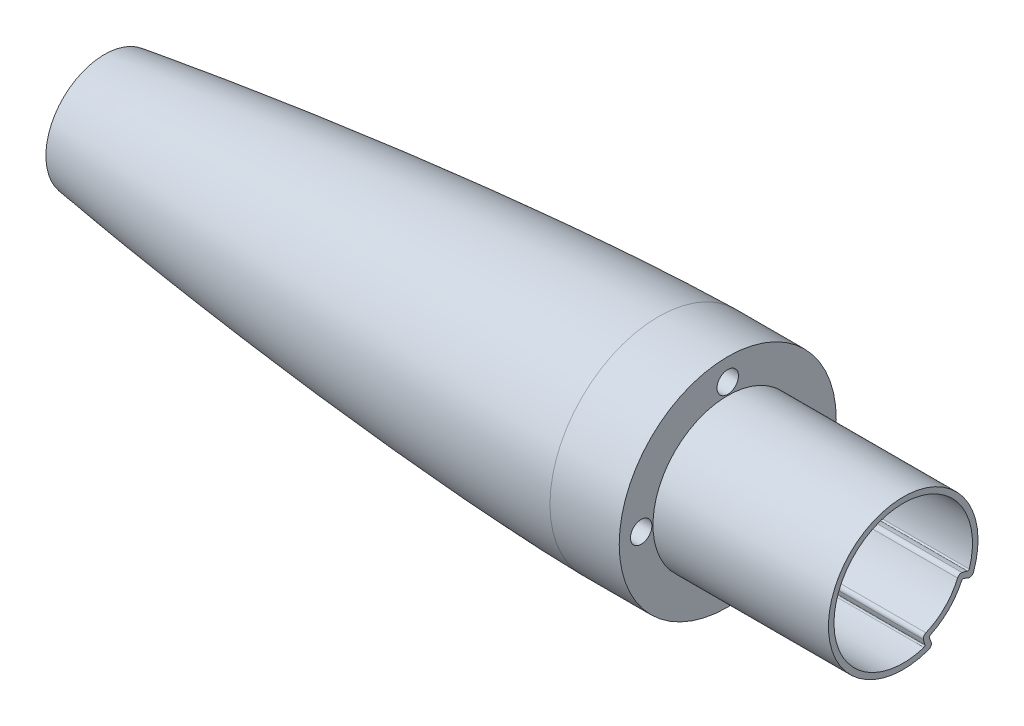
SolidWorks part; units mm, degrees
ref_plane "Front Plane" through (0, 0, 0) normal (0, 0, 1) x (1, 0, 0)
ref_plane "Top Plane" through (0, 0, 0) normal (0, 1, 0) x (1, 0, 0)
ref_plane "Right Plane" through (0, 0, 0) normal (1, 0, 0) x (0, 0, -1)
sketch "Sketch1" plane through (0, 0, 0) normal (0, 0, 1) x (1, 0, 0)
  line L0 (0, 0) -> (600, 0) construction
  line L1 (600, 0) -> (600, 78.36) construction
  line L2 (600, 78.36) -> (650, 78.36)
  line L3 (650, 78.36) -> (650, 54)
  line L4 (650, 54) -> (776.72, 54)
  line L5 (776.72, 54) -> (776.72, 0)
  line L6 (776.72, 0) -> (0, 0)
  line L7 (200, 0) -> (200, 42.3283)
  circle A0 centre (72.0133, 0) radius 20
  spline S0 degree 4 poles (0, 0) (0.0016, 0.0064) (0.0058, 0.0188) (0.0175, 0.0422) (0.0463, 0.0862) (0.0915, 0.1423) (0.1543, 0.2091) (0.2763, 0.3247) (0.4211, 0.4433) (0.5863, 0.5665) (0.8395, 0.741) (1.183, 0.9602) (1.7828, 1.3087) (2.8683, 1.8716) (4.7628, 2.7397) (8.1903, 4.116) (14.423, 6.288) (24.8043, 9.4077) (38.8995, 13.0876) (55.9277, 17.0568) (79.0908, 21.9784) (106.8812, 27.3296) (139.4042, 33.0214) (176.6683, 38.9539) (214.0039, 44.4169) (251.3968, 49.4711) (288.8378, 54.1545) (326.3207, 58.4893) (363.8412, 62.4863) (401.396, 66.1465) (438.983, 69.4606) (476.6007, 72.4071) (509.5423, 74.6287) (537.7965, 76.2335) (560.2923, 77.2755) (575.1954, 77.8326) (587.2142, 78.173) (594.52, 78.3104) (598.1733, 78.3543) (600, 78.36) knots 0 0 0 0 0 0.000043 0.000086 0.000173 0.000345 0.000518 0.00069 0.00128 0.001578 0.001875 0.002717 0.003965 0.006149 0.009932 0.016448 0.028301 0.04964 0.081363 0.112452 0.14354 0.205717 0.267893 0.33007 0.392247 0.454423 0.5166 0.578777 0.640954 0.70313 0.765307 0.827484 0.88966 0.920749 0.951837 0.975919 0.987959 1 1 1 1 1 construction
  spline S1 degree 4 poles (0, 0) (0.0016, 0.0064) (0.0058, 0.0188) (0.0175, 0.0422) (0.0463, 0.0862) (0.0915, 0.1423) (0.1543, 0.2091) (0.2763, 0.3247) (0.4211, 0.4433) (0.5863, 0.5665) (0.8395, 0.741) (1.183, 0.9602) (1.7828, 1.3087) (2.8683, 1.8716) (4.7628, 2.7397) (8.1903, 4.116) (14.423, 6.288) (24.8043, 9.4077) (38.8995, 13.0876) (55.9277, 17.0568) (79.0908, 21.9784) (106.8812, 27.3296) (139.4042, 33.0214) (176.6683, 38.9539) (214.0039, 44.4169) (251.3968, 49.4711) (288.8378, 54.1545) (326.3207, 58.4893) (363.8412, 62.4863) (401.396, 66.1465) (438.983, 69.4606) (476.6007, 72.4071) (509.5423, 74.6287) (537.7965, 76.2335) (560.2923, 77.2755) (575.1954, 77.8326) (587.2142, 78.173) (594.52, 78.3104) (598.1733, 78.3543) (600, 78.36) knots 0 0 0 0 0 0.000043 0.000086 0.000173 0.000345 0.000518 0.00069 0.00128 0.001578 0.001875 0.002717 0.003965 0.006149 0.009932 0.016448 0.028301 0.04964 0.081363 0.112452 0.14354 0.205717 0.267893 0.33007 0.392247 0.454423 0.5166 0.578777 0.640954 0.70313 0.765307 0.827484 0.88966 0.920749 0.951837 0.975919 0.987959 1 1 1 1 1
  dimension "D6" = 40
  dimension "D1" = 78.36
  dimension "D2" = 54
  dimension "D3" = 126.72
  dimension "D4" = 50
  dimension "D5" = 200
revolve "Revolve1" add sketch "Sketch1" angle 360 about L6 region at (496.4687, 32.5271, 0)
sketch "Sketch2" plane through (776.72, 0, 0) normal (1, 0, 0) x (0, 0, -1)
  line L0 (38.1838, -38.1838) -> (0, 0) construction
  line L1 (0, 0) -> (54, 0) construction
  circle A0 centre (0, 0) radius 50
  circle A1 centre (0, 0) radius 54 construction
  circle A2 centre (38.1838, -38.1838) radius 20
  circle A3 centre (0, 0) radius 54 construction
  circle A4 centre (0, 0) radius 42.5
  circle A5 centre (38.1838, -38.1838) radius 24
  circle A6 centre (0, 0) radius 46.5
  circle M1 centre (0, 0) radius 54
  dimension "D1" = 4
  dimension "D3" = 40
  dimension "D4" = 85
  dimension "D5" = 4
  dimension "D2" = 45
  dimension "D6" = 4
extrude "Cut-Extrude1" cut sketch "Sketch2" against normal blind 400 contours A5 A4 | A5 A6 A4 | A6 A5 A0 | A2 A4 | A4 A5 A2 region at (776.72, -7.8832, -47.942) region at (776.72, 26.3344, 36.7174) region at (776.72, -21.4717, -21.4717) region at (776.72, 1.5125, 1.5125) region at (776.72, -27.2667, -27.2667)
sketch "Sketch3" plane through (200, 0, 0) normal (-1, 0, 0) x (0, 0, 1)
  circle A0 centre (0, 20) radius 3.1
  circle A1 centre (0, -20) radius 3.1
  circle A2 centre (0, 0) radius 20 construction
  circle A3 centre (0, 0) radius 33
  dimension "D1" = 6.2
  dimension "D2" = 40
  dimension "D3" = 13
extrude "Cut-Extrude2" cut sketch "Sketch3" against normal blind 40
extrude "Cut-Extrude4" cut sketch "Sketch3<2>" against normal through all contours A0 | A1 region at (200, 20, 0) region at (200, -20, 0)
sketch "Sketch3<2>" plane through (200, 0, 0) normal (-1, 0, 0) x (0, 0, 1) same geometry as "Sketch3"
sketch "Sketch4" plane through (650, 0, 0) normal (1, 0, 0) x (0, 0, -1)
  circle A0 centre (0, 0) radius 62.5 construction
  circle A1 centre (0, 62.5) radius 7.75
  circle A2 centre (62.5, 0) radius 7.75
  circle A3 centre (0, -62.5) radius 7.75
  circle A4 centre (-62.5, 0) radius 7.75
  point P14 (0, 0)
  dimension "D1" = 15.5
  dimension "D2" = 125
  dimension "D3" = 4
extrude "Cut-Extrude5" cut sketch "Sketch4" against normal blind 30
extrude "Cut-Extrude6" cut sketch "Sketch2<3>" against normal offset from surface (166.72 mm away) 40 contours A6 A2 A0 | A2 A0 M1 region at (776.72, -33.3337, -33.3337) region at (776.72, -35.9177, -35.9177) up to face at (650, 62.5, -7.75) offset beyond the face yes
sketch "Sketch2<3>" plane through (776.72, 0, 0) normal (1, 0, 0) x (0, 0, -1) same geometry as "Sketch2"
extrude "Cut-Extrude7" cut sketch "Sketch2<4>" against normal blind 40 from surface contours A2 M1 region at (776.72, -43.6895, -43.6895) starting at face at (650, 62.5, -7.75)
sketch "Sketch2<4>" plane through (776.72, 0, 0) normal (1, 0, 0) x (0, 0, -1) same geometry as "Sketch2"
fillet "Fillet1" radius 3 4 edges at (576.72, -40.0379, -14.2555) (576.72, -14.2555, -40.0379) (713.36, -49.4624, -21.6673) (713.36, -21.6673, -49.4624)
fillet "Fillet2" radius 1 4 edges at (693.36, -18.6742, -42.5855) (693.36, -42.5855, -18.6742) (576.72, -16.0103, -47.3674) (576.72, -47.3674, -16.0103)
